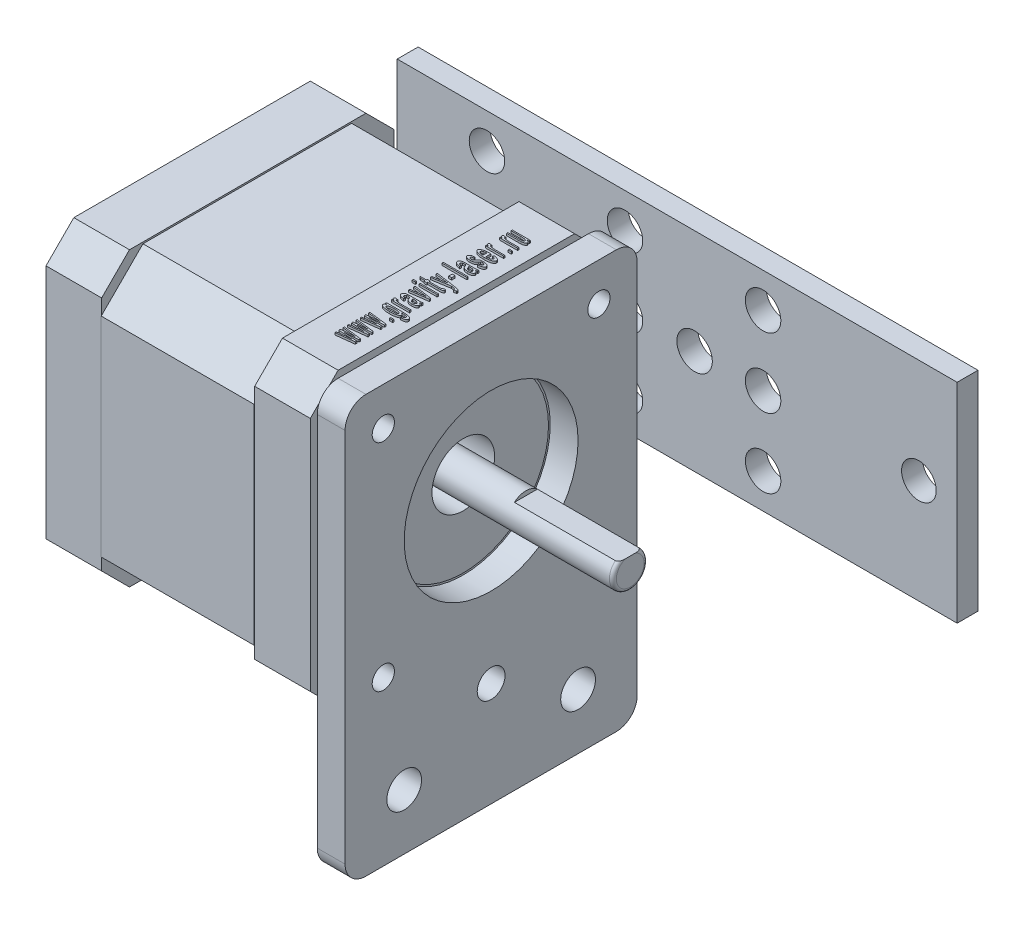
SolidWorks part; units mm, degrees
ref_plane "Спереди" through (0, 0, 0) normal (0, 0, 1) x (1, 0, 0)
ref_plane "Сверху" through (0, 0, 0) normal (0, 1, 0) x (1, 0, 0)
ref_plane "Справа" through (0, 0, 0) normal (1, 0, 0) x (0, 0, -1)
ref_plane "Плоскость1" through (0, 0, 0) normal (1, 0, 0) x (0, 0, -1)
sketch "Эскиз1" plane through (0, 0, 0) normal (1, 0, 0) x (0, 0, -1)
  line L0 (21, 60) -> (21, 39) construction
  line L1 (3, 0) -> (39, 0)
  line L2 (0, 3) -> (0, 57)
  line L3 (3, 60) -> (39, 60)
  line L4 (42, 3) -> (42, 57)
  line L5 (21, 39) -> (21, 54.5) construction
  line L6 (21, 39) -> (21, 23.5) construction
  line L7 (21, 23.5) -> (5.5, 23.5) construction
  line L8 (5.5, 23.5) -> (5.5, 54.5) construction
  line L9 (5.5, 54.5) -> (21, 54.5) construction
  line L10 (21, 0) -> (21, 8) construction
  line L11 (21, 8) -> (8.5, 8) construction
  line L12 (8.5, 8) -> (33.5, 8) construction
  circle A0 centre (21, 39) radius 12.5
  circle A1 centre (5.5, 54.5) radius 1.6
  circle A2 centre (5.5, 23.5) radius 1.6
  circle A3 centre (36.5, 23.5) radius 1.6
  circle A4 centre (36.5, 54.5) radius 1.6
  circle A5 centre (8.5, 8) radius 2.5
  circle A6 centre (33.5, 8) radius 2.5
  arc A7 (0, 57) -> (3, 60) centre (3, 57) cw
  arc A8 (0, 3) -> (3, 0) centre (3, 3) ccw
  arc A9 (39, 0) -> (42, 3) centre (39, 3) ccw
  arc A10 (42, 57) -> (39, 60) centre (39, 57) ccw
  point P28 (0, 0)
  point P31 (42, 0)
  point P34 (42, 60)
  dimension "D3" = 25
  dimension "D8" = 3.2
  dimension "D9" = 3.2
  dimension "D11" = 5
  dimension "D13" = 3
  dimension "D1" = 42
  dimension "D2" = 60
  dimension "D4" = 21
  dimension "D5" = 15.5
  dimension "D6" = 15.5
  dimension "D7" = 31
  dimension "D10" = 8
  dimension "D12" = 12.5
extrude "Бобышка-Вытянуть1" add sketch "Эскиз1" along normal blind 4
ref_plane "Плоскость2" through (0, 0, -80) normal (0, 0, 1) x (1, 0, 0)
sketch "Эскиз2" plane through (0, 0, -80) normal (0, 0, 1) x (1, 0, 0)
  line L0 (-32.75, 15) -> (-32.75, 30) construction
  line L1 (0, 30) -> (-65.5, 30)
  line L2 (-32.75, 15) -> (-32.75, 0) construction
  line L3 (-65.5, 30) -> (-65.5, 0)
  line L4 (-65.5, 0) -> (0, 0)
  line L5 (0, 30) -> (0, 0)
  circle A0 centre (-22.75, 15) radius 2.55
  circle A1 centre (-12.9, 5) radius 2.55
  circle A2 centre (-12.9, 15) radius 2.55
  circle A3 centre (-12.9, 25) radius 2.55
  circle A4 centre (-42.75, 15) radius 2.55
  circle A5 centre (-52.6, 15) radius 2.55
  circle A6 centre (-52.6, 25) radius 2.55
  circle A7 centre (-52.6, 5) radius 2.55
  circle A8 centre (-32.75, 15) radius 2.55
  circle A9 centre (-32.75, 25) radius 2.55
  circle A10 centre (-32.75, 5) radius 2.55
  dimension "D1" = 5.1
  dimension "D2" = 5.1
  dimension "D3" = 5.1
  dimension "D7" = 5.1
  dimension "D4" = 15
  dimension "D5" = 15
  dimension "D6" = 32.75
extrude "Бобышка-Вытянуть2" add sketch "Эскиз2" along normal blind 3 separate body
sketch "Эскиз3" plane through (0, 0, -80) normal (0, 0, 1) x (1, 0, 0)
  line L1 (0, 0) -> (15, 0)
  line L2 (0, 0) -> (0, 30)
  line L3 (0, 30) -> (15, 30)
  line L4 (15, 0) -> (15, 30)
  dimension "D1" = 15
  dimension "D2" = 30
extrude "Бобышка-Вытянуть3" add sketch "Эскиз3" along normal blind 3
ref_plane "Плоскость3" through (0, 0, -80) normal (0, 0, -1) x (-1, 0, 0)
sketch "Эскиз4" plane through (0, 0, -80) normal (0, 0, -1) x (-1, 0, 0)
  line L0 (-15, 30) -> (-4, 30) construction
  line L1 (-4, 3) -> (-4, 57) construction
  line L2 (-4, 30) -> (-9.5, 30) construction
  line L3 (-9.5, 30) -> (-9.5, 0) construction
  line L4 (65.5, 0) -> (-15, 0) construction
  circle A0 centre (-9.5, 15) radius 2.4923
  dimension "D1" = 4.9846
extrude "Вырез-Вытянуть1" cut sketch "Эскиз4" against normal blind 10
ref_plane "Плоскость4" through (4, 0, 0) normal (1, 0, 0) x (0, 0, -1)
sketch "Эскиз5" plane through (4, 0, 0) normal (1, 0, 0) x (0, 0, -1)
  line L0 (0, 0) -> (42, 0) construction
  line L1 (42, 0) -> (21, 0) construction
  line L2 (21, 0) -> (21, 15) construction
  circle A0 centre (21, 15) radius 2
  dimension "D1" = 4
extrude "Вырез-Вытянуть2" cut sketch "Эскиз5" against normal blind 10 and the other way blind 10
ref_plane "Плоскость5" through (-1, 0, 0) normal (-1, 0, 0) x (0, 0, 1)
sketch "Эскиз6" plane through (-1, 0, 0) normal (-1, 0, 0) x (0, 0, 1)
  line L0 (-42, 60) -> (-38, 60) construction
  line L1 (-42, 60) -> (0, 60) construction
  line L2 (-42, 60) -> (-42, 18) construction
  line L3 (-42, 18) -> (0, 18) construction
  line L4 (0, 60) -> (0, 18) construction
  line L5 (-42, 60) -> (0, 18) construction
  line L6 (-42, 18) -> (0, 60) construction
  line L7 (-42, 60) -> (-42, 56) construction
  line L8 (-42, 56) -> (-38, 60)
  line L9 (-21, 39) -> (-42, 39) construction
  line L10 (-21, 39) -> (-21, 60) construction
  line L11 (0, 56) -> (-4, 60)
  line L12 (0, 22) -> (-4, 18)
  line L13 (-42, 22) -> (-38, 18)
  line L14 (-38, 60) -> (-4, 60)
  line L15 (0, 56) -> (0, 22)
  line L16 (-4, 18) -> (-38, 18)
  line L17 (-42, 22) -> (-42, 56)
  point P0 (-21, 39)
  dimension "D1" = 42
  dimension "D2" = 42
  dimension "D3" = 4
  dimension "D4" = 4
extrude "Бобышка-Вытянуть4" add sketch "Эскиз6" along normal blind 8 separate body
ref_plane "Плоскость6" through (-9, 0, 0) normal (-1, 0, 0) x (0, 0, 1)
sketch "Эскиз7" plane through (-9, 0, 0) normal (-1, 0, 0) x (0, 0, 1)
  line L0 (-41.9404, 59.7724) -> (-35.9404, 59.7724) construction
  line L1 (-41.9404, 59.7724) -> (0.0596, 59.7724) construction
  line L2 (-41.9404, 59.7724) -> (-41.9404, 17.7724) construction
  line L3 (-41.9404, 17.7724) -> (0.0596, 17.7724) construction
  line L4 (0.0596, 59.7724) -> (0.0596, 17.7724) construction
  line L5 (-41.9404, 59.7724) -> (0.0596, 17.7724) construction
  line L6 (-41.9404, 17.7724) -> (0.0596, 59.7724) construction
  line L7 (-41.9404, 59.7724) -> (-41.9404, 53.7724) construction
  line L8 (-41.9404, 53.7724) -> (-35.9404, 59.7724)
  line L9 (-20.9404, 38.7724) -> (-41.9404, 38.7724) construction
  line L10 (-20.9404, 38.7724) -> (-20.9404, 59.7724) construction
  line L11 (0.0596, 53.7724) -> (-5.9404, 59.7724)
  line L12 (0.0596, 23.7724) -> (-5.9404, 17.7724)
  line L13 (-41.9404, 23.7724) -> (-35.9404, 17.7724)
  line L14 (-35.9404, 59.7724) -> (-5.9404, 59.7724)
  line L15 (0.0596, 53.7724) -> (0.0596, 23.7724)
  line L16 (-5.9404, 17.7724) -> (-35.9404, 17.7724)
  line L17 (-41.9404, 23.7724) -> (-41.9404, 53.7724)
  point P0 (-20.9404, 38.7724)
  dimension "D1" = 42
  dimension "D2" = 42
  dimension "D3" = 6
  dimension "D4" = 6
extrude "Бобышка-Вытянуть5" add sketch "Эскиз7" along normal blind 22
ref_plane "Плоскость7" through (-31, 0, 0) normal (-1, 0, 0) x (0, 0, 1)
sketch "Эскиз8" plane through (-31, 0, 0) normal (-1, 0, 0) x (0, 0, 1)
  line L0 (-42, 60) -> (-38, 60) construction
  line L1 (-42, 60) -> (0, 60) construction
  line L2 (-42, 60) -> (-42, 18) construction
  line L3 (-42, 18) -> (0, 18) construction
  line L4 (0, 60) -> (0, 18) construction
  line L5 (-42, 60) -> (0, 18) construction
  line L6 (-42, 18) -> (0, 60) construction
  line L7 (-42, 60) -> (-42, 56) construction
  line L8 (-42, 56) -> (-38, 60)
  line L9 (-21, 39) -> (-42, 39) construction
  line L10 (-21, 39) -> (-21, 60) construction
  line L11 (0, 56) -> (-4, 60)
  line L12 (0, 22) -> (-4, 18)
  line L13 (-42, 22) -> (-38, 18)
  line L14 (-38, 60) -> (-4, 60)
  line L15 (0, 56) -> (0, 22)
  line L16 (-4, 18) -> (-38, 18)
  line L17 (-42, 22) -> (-42, 56)
  point P0 (-21, 39)
  dimension "D1" = 42
  dimension "D2" = 42
  dimension "D3" = 4
  dimension "D4" = 4
extrude "Бобышка-Вытянуть6" add sketch "Эскиз8" along normal blind 8
ref_plane "Плоскость8" through (-39, 0, 0) normal (-1, 0, 0) x (0, 0, 1)
sketch "Эскиз9" plane through (-39, 0, 0) normal (-1, 0, 0) x (0, 0, 1)
  circle A0 centre (-21, 39) radius 4.5
  dimension "D1" = 9
extrude "Вырез-Вытянуть3" cut sketch "Эскиз9" against normal blind 88
ref_plane "Плоскость9" through (-1, 0, 0) normal (1, 0, 0) x (0, 0, -1)
sketch "Эскиз10" plane through (-1, 0, 0) normal (1, 0, 0) x (0, 0, -1)
  circle A0 centre (21, 39) radius 12.25
  circle A1 centre (21, 39) radius 4.5
  dimension "D1" = 24.5
  dimension "D2" = 9
extrude "Бобышка-Вытянуть7" add sketch "Эскиз10" along normal blind 1
ref_plane "Плоскость10" through (-35, 0, 0) normal (1, 0, 0) x (0, 0, -1)
sketch "Эскиз11" plane through (-35, 0, 0) normal (1, 0, 0) x (0, 0, -1)
  circle A0 centre (21, 39) radius 4
  circle A1 centre (21, 39) radius 2.5
  dimension "D1" = 8
  dimension "D2" = 5
extrude "Бобышка-Вытянуть8" add sketch "Эскиз11" along normal blind 30 separate body
ref_plane "Плоскость11" through (-35, 0, 0) normal (1, 0, 0) x (0, 0, -1)
sketch "Эскиз12" plane through (-35, 0, 0) normal (1, 0, 0) x (0, 0, -1)
  circle A0 centre (21, 39) radius 2.495
  dimension "D1" = 4.99
extrude "Бобышка-Вытянуть9" add sketch "Эскиз12" along normal blind 59 separate body
ref_plane "Плоскость12" through (0, 0, -21) normal (0, 0, 1) x (1, 0, 0)
sketch "Эскиз14" plane through (0, 0, -21) normal (0, 0, 1) x (1, 0, 0)
  line L0 (24, 41.495) -> (24, 36.505) construction
  line L1 (24, 36.505) -> (24, 39) construction
  line L2 (24, 39) -> (24, 41.495) construction
  line L3 (24, 41.495) -> (24, 39) construction
  line L4 (24, 39) -> (24, 40.2475) construction
  line L5 (24, 40.2475) -> (24, 41.495) construction
  line L6 (24, 41.495) -> (24, 40.8713) construction
  line L7 (24, 40.8713) -> (9, 40.8713) construction
  line L9 (9, 40.8713) -> (25.6583, 40.8713)
  line L10 (9, 40.8713) -> (9, 46.1963)
  line L11 (9, 46.1963) -> (25.6583, 46.1963)
  line L12 (25.6583, 40.8713) -> (25.6583, 46.1963)
  dimension "D1" = 15
fillet "Скругление1" radius 0.5 1 edges at (24, 39, -23.495) type face fillet first side face at (24, 39, -23.495) second side face at (24, 39, -23.495)
extrude "Вырез-Вытянуть4" cut sketch "Эскиз14" against normal blind 55 and the other way blind 55
extrude "Вырез-Вытянуть5" cut sketch "Эскиз1<3>" against normal blind 5 contours A1 | A4 | A3 | A2
sketch "Эскиз1<3>" plane through (0, 0, 0) normal (1, 0, 0) x (0, 0, -1) same geometry as "Эскиз1"
ref_plane "Плоскость13" through (0, 60, 0) normal (0, 1, 0) x (1, 0, 0)
sketch "Эскиз15" plane through (0, 60, 0) normal (0, 1, 0) x (1, 0, 0)
  line L0 (-9, 4) -> (-1, 4) construction
  line L1 (-1, 4) -> (-5, 4) construction
  line L2 (-5, 4) -> (-3, 4) construction
  line L3 (-3, 4) -> (-3, 38) construction
  line L4 (-9, 38) -> (-1, 38) construction
  text T0 "www.gravity-laser.ru" font "Arial" height in points 14
extrude "Бобышка-Вытянуть10" add sketch "Эскиз15" along normal blind 0.3 and the other way blind 1
